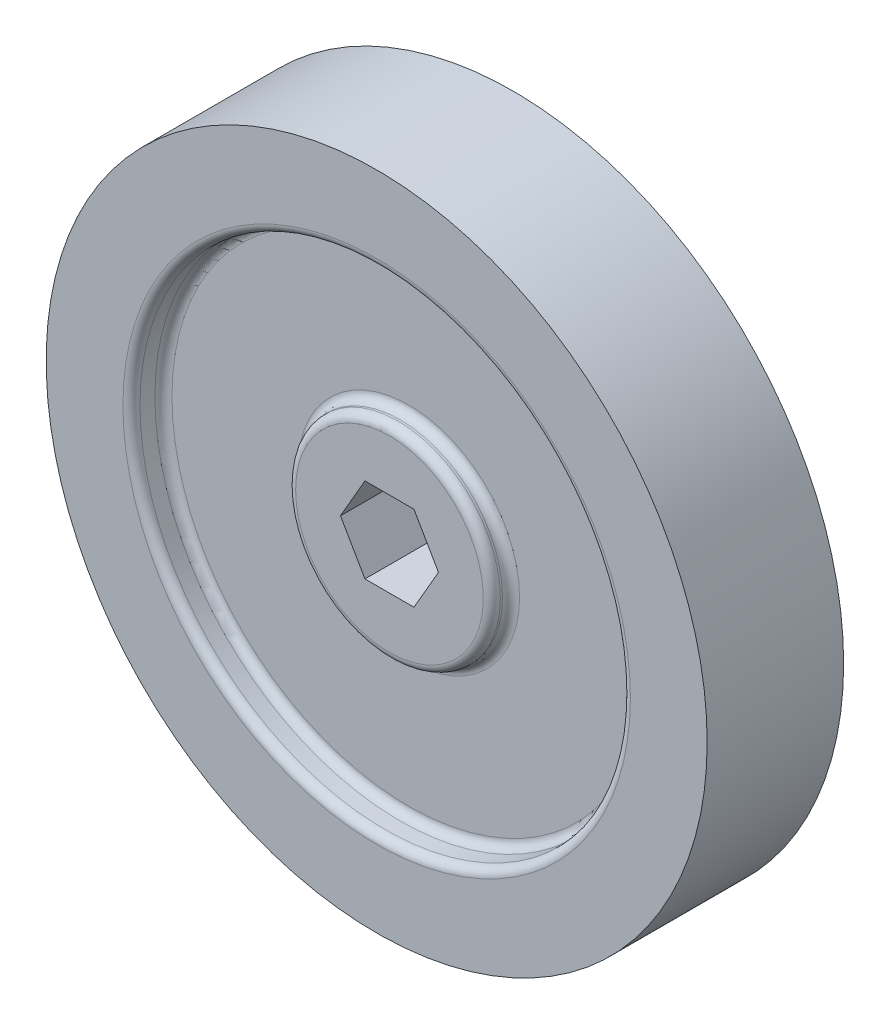
SolidWorks part; units mm, degrees
ref_plane "Front Plane" through (0, 0, 0) normal (0, 0, 1) x (1, 0, 0)
ref_plane "Top Plane" through (0, 0, 0) normal (0, 1, 0) x (1, 0, 0)
ref_plane "Right Plane" through (0, 0, 0) normal (1, 0, 0) x (0, 0, -1)
sketch "Sketch1" plane through (0, 0, 0) normal (0, 0, 1) x (1, 0, 0)
  circle A0 centre (0, 0) radius 49.2125
  dimension "D1" = 98.425
extrude "Boss-Extrude1" add sketch "Sketch1" along normal blind 10.16 and the other way blind 10.16
sketch "Sketch2" plane through (0, 0, 10.16) normal (0, 0, 1) x (1, 0, 0)
  line L1 (3.6489, 6.32) -> (-3.6489, 6.32)
  line L2 (-3.6489, 6.32) -> (-7.2977, 0)
  line L3 (-7.2977, 0) -> (-3.6489, -6.32)
  line L4 (-3.6489, -6.32) -> (3.6489, -6.32)
  line L5 (3.6489, -6.32) -> (7.2977, 0)
  line L6 (7.2977, 0) -> (3.6489, 6.32)
  circle A0 centre (0, 0) radius 6.32 construction
  dimension "D1" = 12.64
extrude "Cut-Extrude1" cut sketch "Sketch2" against normal through all
sketch "Sketch3" plane through (0, 0, 0) normal (1, 0, 0) x (0, 0, -1)
  line L0 (8.255, 15.24) -> (5.3975, 15.24)
  line L1 (10.16, -49.2125) -> (10.16, 49.2125) construction
  line L2 (5.3975, 15.24) -> (5.3975, 36.5125)
  line L3 (5.3975, 36.5125) -> (10.16, 36.5125)
  line L4 (10.16, 36.5125) -> (10.16, 0)
  line L5 (22.753, 0) -> (-27.7028, 0) construction
  line L6 (10.16, 49.2125) -> (-10.16, 49.2125) construction
  line L7 (10.16, 0) -> (8.255, 0)
  line L8 (8.255, 0) -> (8.255, 15.24)
  dimension "D1" = 21.2725
  dimension "D2" = 12.7
  dimension "D3" = 1.905
  dimension "D4" = 4.7625
revolve "Cut-Revolve1" cut sketch "Sketch3" angle 360 about L5
fillet "Fillet1" radius 1.27 3 edges at (-15.24, 0, -5.3975) (-36.5125, 0, -10.16) (-15.24, 0, -8.255)
mirror "Mirror1" about plane through (0, 0, 0) normal (0, 0, 1) of "Cut-Revolve1"
fillet "Fillet2" radius 1.27 4 edges at (-36.5125, 0, 10.16) (-36.5125, 0, 5.3975) (-15.24, 0, 5.3975) (-15.24, 0, 8.255)
